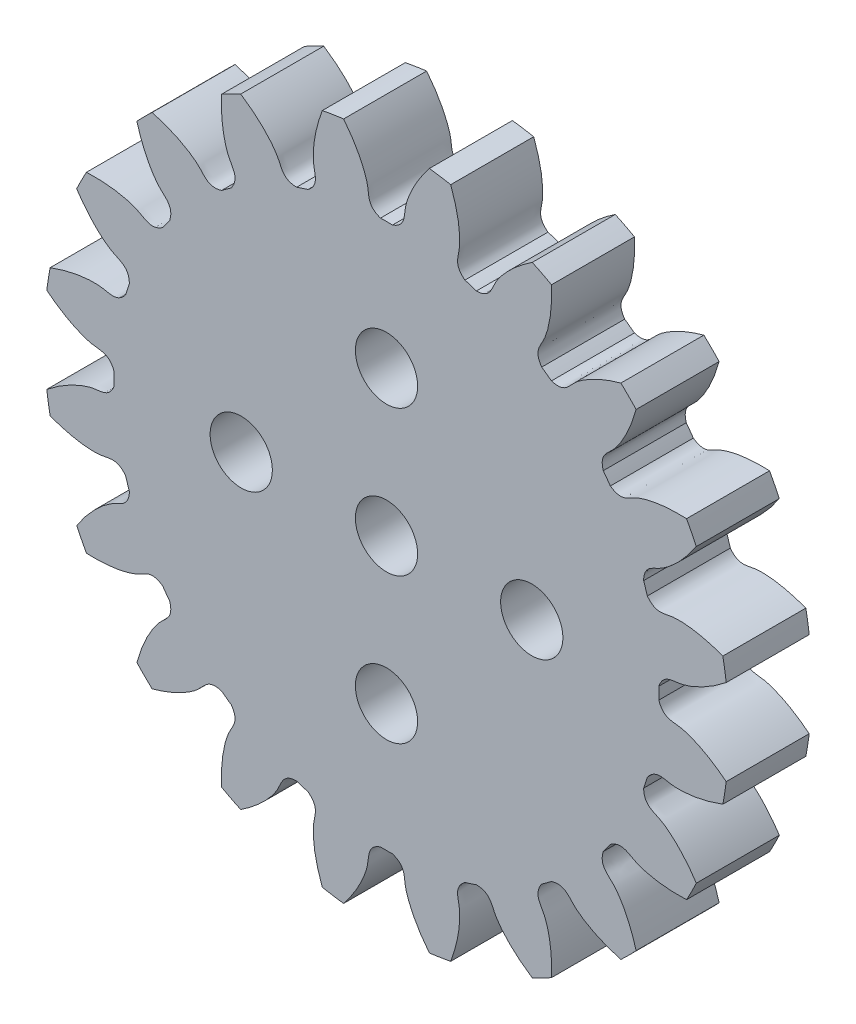
SolidWorks part; units mm, degrees
material "Thornel Mat VMA"
ref_plane "前视基准面" through (0, 0, 0) normal (0, 0, 1) x (1, 0, 0)
ref_plane "上视基准面" through (0, 0, 0) normal (0, 1, 0) x (1, 0, 0)
ref_plane "右视基准面" through (0, 0, 0) normal (1, 0, 0) x (0, 0, -1)
other "Configuration Table"
sketch "草图1" plane through (0, 0, 0) normal (0, 0, 1) x (1, 0, 0)
  circle A0 centre (0, 0) radius 16.5
extrude "凸台-拉伸1" add sketch "草图1" along normal blind 4
ref_axis "基准轴1" through (0, 0, -1.5) along (0, 0, 1)
sketch "草图2" plane through (0, 0, 0) normal (0, 0, 1) x (1, 0, 0)
  line L0 (0, 0) -> (0, 16.5) construction
  circle A0 centre (0, 0) radius 16.5 construction
  arc A1 (0.29, 13.1218) -> (-0.29, 13.1218) centre (0, 0) ccw
  arc A2 (4.7717, 18.7474) -> (-4.7717, 18.7474) centre (0, 0) ccw
  spline S0 degree 3 poles (0.29, 13.1218) (0.9168, 13.3402) (0.8356, 13.7807) (0.9193, 14.205) (0.9283, 14.2463) (0.9395, 14.293) (0.9529, 14.3448) (0.969, 14.4018) (0.9878, 14.4638) (1.0095, 14.5309) (1.0345, 14.6028) (1.0629, 14.6795) (1.0948, 14.7608) (1.1305, 14.8467) (1.1702, 14.9371) (1.2141, 15.0317) (1.2623, 15.1305) (1.315, 15.2334) (1.3725, 15.3401) (1.4349, 15.4506) (1.5023, 15.5646) (1.575, 15.6821) (1.653, 15.8029) (1.7366, 15.9267) (1.826, 16.0534) (1.9211, 16.1829) (2.0223, 16.3149) (2.1296, 16.4493) (2.2432, 16.5859) (2.3632, 16.7244) (2.4897, 16.8646) (2.6229, 17.0065) (2.7628, 17.1496) (2.9095, 17.2939) (3.0632, 17.4391) (3.224, 17.585) (3.3918, 17.7313) (3.567, 17.8779) (3.7493, 18.0245) (3.9391, 18.1709) (4.1363, 18.3167) (4.4122, 18.5125) (4.6259, 18.6545) (4.7717, 18.7474) knots 0 0 0 0 0.165916 0.170906 0.176664 0.183189 0.190482 0.198542 0.207371 0.216967 0.22733 0.238462 0.250361 0.263027 0.276462 0.290664 0.305634 0.321371 0.337876 0.355149 0.37319 0.391998 0.411574 0.431917 0.453028 0.474907 0.497554 0.520968 0.54515 0.570099 0.595817 0.622302 0.649554 0.677575 0.706363 0.735918 0.766242 0.797333 0.829191 0.861818 0.895212 0.929373 1 1 1 1
  spline S1 degree 3 poles (-0.29, 13.1218) (-0.9168, 13.3402) (-0.8356, 13.7807) (-0.9193, 14.205) (-0.9283, 14.2463) (-0.9395, 14.293) (-0.9529, 14.3448) (-0.969, 14.4018) (-0.9878, 14.4638) (-1.0095, 14.5309) (-1.0345, 14.6028) (-1.0629, 14.6795) (-1.0948, 14.7608) (-1.1305, 14.8467) (-1.1702, 14.9371) (-1.2141, 15.0317) (-1.2623, 15.1305) (-1.315, 15.2334) (-1.3725, 15.3401) (-1.4349, 15.4506) (-1.5023, 15.5646) (-1.575, 15.6821) (-1.653, 15.8029) (-1.7366, 15.9267) (-1.826, 16.0534) (-1.9211, 16.1829) (-2.0223, 16.3149) (-2.1296, 16.4493) (-2.2432, 16.5859) (-2.3632, 16.7244) (-2.4897, 16.8646) (-2.6229, 17.0065) (-2.7628, 17.1496) (-2.9095, 17.2939) (-3.0632, 17.4391) (-3.224, 17.585) (-3.3918, 17.7313) (-3.567, 17.8779) (-3.7493, 18.0245) (-3.9391, 18.1709) (-4.1363, 18.3167) (-4.4122, 18.5125) (-4.6259, 18.6545) (-4.7717, 18.7474) knots 0 0 0 0 0.165916 0.170906 0.176664 0.183189 0.190482 0.198542 0.207371 0.216967 0.22733 0.238462 0.250361 0.263027 0.276462 0.290664 0.305634 0.321371 0.337876 0.355149 0.37319 0.391998 0.411574 0.431917 0.453028 0.474907 0.497554 0.520968 0.54515 0.570099 0.595817 0.622302 0.649554 0.677575 0.706363 0.735918 0.766242 0.797333 0.829191 0.861818 0.895212 0.929373 1 1 1 1
extrude "切除-拉伸1" cut sketch "草图2" along normal through all
pattern_circular "阵列(圆周)1" count 20 every 18 about axis through (0, 0, -1.5) along (0, 0, 1) of "切除-拉伸1"
sketch "草图3" plane through (0, 0, 0) normal (0, 0, 1) x (1, 0, 0)
  circle A0 centre (0, 0) radius 15 construction
  dimension "Dn" = 30
sketch "草图4" plane through (0, 0, 4) normal (0, 0, 1) x (1, 0, 0)
  line L0 (0, 0) -> (0, 21.3369) construction
  line L1 (0, 0) -> (36.3536, 0) construction
  circle A0 centre (0, 7) radius 1.5
  circle A1 centre (0, 0) radius 1.5
  circle A2 centre (7, 0) radius 1.5
  circle A3 centre (0, -7) radius 1.5
  circle A4 centre (-7, 0) radius 1.5
  dimension "D1" = 3
  dimension "D2" = 3
  dimension "D3" = 3
  dimension "D4" = 7
  dimension "D5" = 7
extrude "切除-拉伸2" cut sketch "草图4" against normal blind 10
